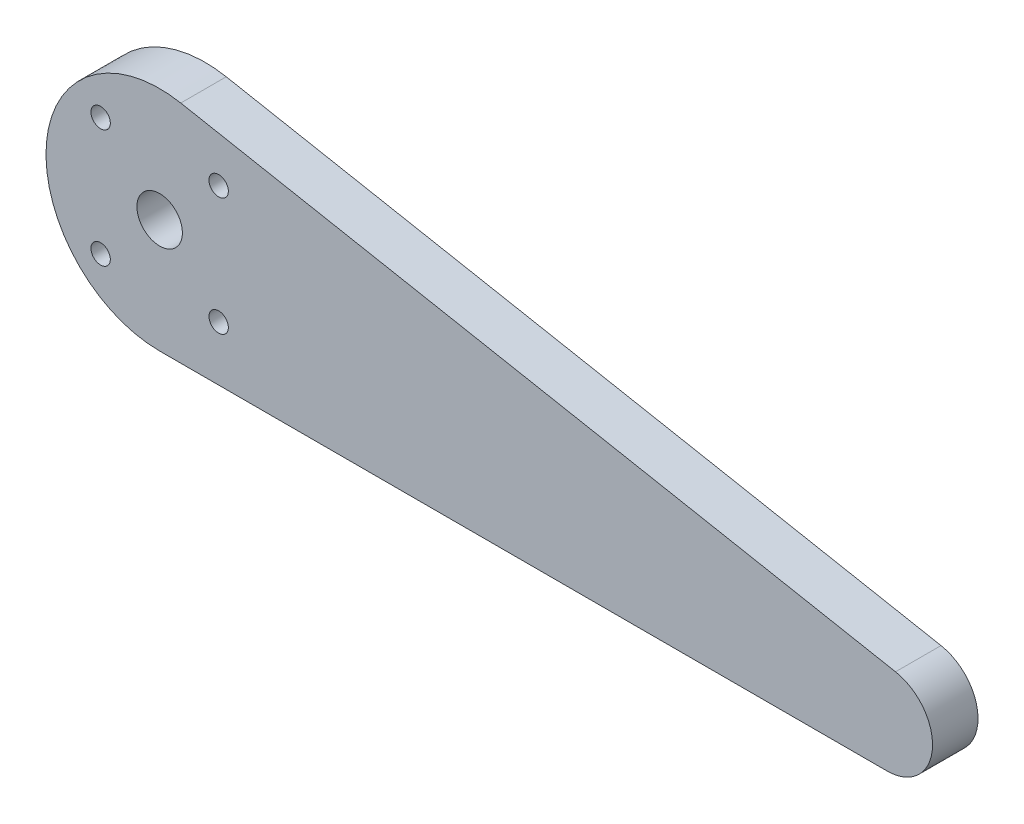
SolidWorks part; units mm, degrees
material "6061 Alloy"
ref_plane "Front" through (0, 0, 0) normal (0, 0, 1) x (1, 0, 0)
ref_plane "Top" through (0, 0, 0) normal (0, 1, 0) x (1, 0, 0)
ref_plane "Right" through (0, 0, 0) normal (1, 0, 0) x (0, 0, -1)
sketch "Sketch1" plane through (0, 0, 0) normal (0, 0, 1) x (1, 0, 0)
  line L0 (0, -15.875) -> (101.6, -15.875)
  line L1 (2.9506, 15.5984) -> (102.7803, -3.2856)
  line L2 (8.2424, 8.2424) -> (-8.2424, -8.2424) construction
  line L3 (-8.2424, 8.2424) -> (8.2424, -8.2424) construction
  arc A0 (2.9506, 15.5984) -> (0, -15.875) centre (0, 0) ccw
  circle A1 centre (0, 0) radius 3.175
  circle A6 centre (0, 0) radius 11.6565 construction
  circle A7 centre (8.2424, 8.2424) radius 1.3525 construction
  circle A8 centre (-8.2424, 8.2424) radius 1.3525 construction
  circle A9 centre (-8.2424, -8.2424) radius 1.3525 construction
  circle A10 centre (8.2424, -8.2424) radius 1.3525 construction
  arc A11 (101.6, -15.875) -> (102.7803, -3.2856) centre (101.6, -9.525) ccw
  dimension "D1" = 6.35
  dimension "D2" = 31.75
  dimension "D3" = 6.35
  dimension "D4" = 101.6
  dimension "D7" = 23.313
  dimension "D8" = 2.7051
extrude "Boss-Extrude1" add sketch "Sketch1" along normal blind 6.35
hole_wizard "#6-32 Tapped Hole1" positions "Sketch2" profile "Sketch3" tap size "#6-32" standard "ANSI Inch" end condition through all
sketch "Sketch2" plane through (0, 0, 6.35) normal (0, 0, 1) x (1, 0, 0)
  point P0 (8.2424, 8.2424)
  point P3 (-8.2424, 8.2424)
  point P6 (8.2424, -8.2424)
  point P9 (-8.2424, -8.2424)
sketch "Sketch3" plane through (8.2424, 8.2424, 6.35) normal (1, 0, 0) x (0, -1, 0)
  line L0 (0, 0) -> (0, 6.35)
  line L1 (0, 6.35) -> (1.3525, 6.35)
  line L2 (1.3525, 6.35) -> (1.3525, 0)
  line L5 (1.3525, 0) -> (0, 0)
  line L11 (0, -6.35) -> (0, 107.95) construction
  dimension "Thru Tap Drill Dia." = 2.7051
  dimension "Thru Tap Drill Depth" = 6.35
sketch "Sketch4" [suppressed] plane through (0, 0, 6.35) normal (0, 0, 1) x (1, 0, 0)
  circle A0 centre (0, 0) radius 3.175
  circle A1 centre (0, 0) radius 7
  dimension "D1" = 6.35
  dimension "D2" = 14
extrude "Boss-Extrude2" [suppressed] add sketch "Sketch4" along normal blind 1.5875
sketch "Sketch5" plane through (0, 0, 0) normal (0, 0, -1) x (-1, 0, 0)
  circle A0 centre (0, 0) radius 7
  circle A2 centre (0, 0) radius 3.175 construction
  circle A3 centre (0, 0) radius 3.175
  dimension "D2" = 14
extrude "Boss-Extrude3" add sketch "Sketch5" along normal blind 1.5875
